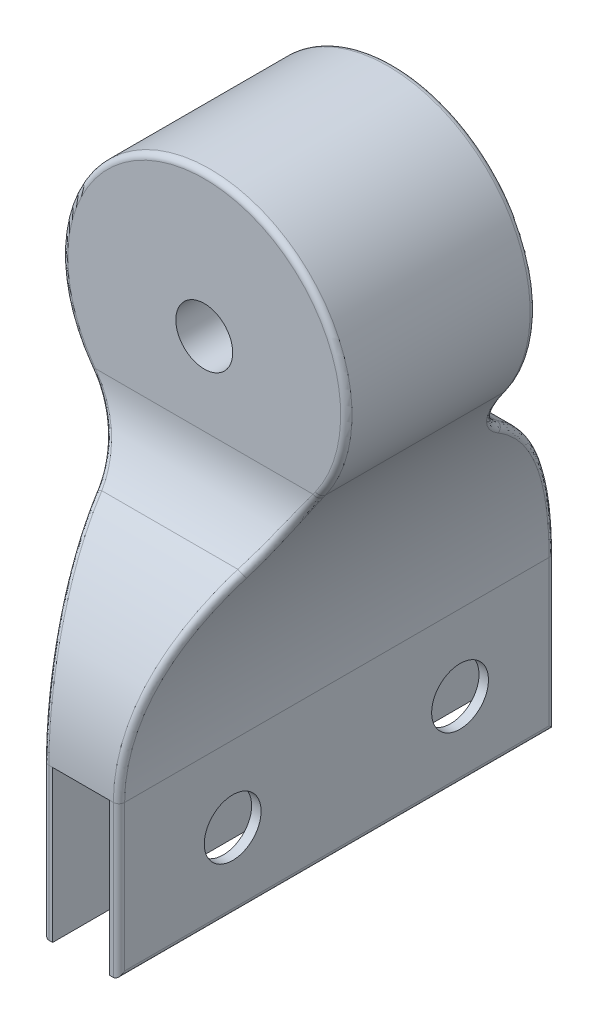
SolidWorks part; units mm, degrees
ref_plane "Front Plane" through (0, 0, 0) normal (0, 0, 1) x (1, 0, 0)
ref_plane "Top Plane" through (0, 0, 0) normal (0, 1, 0) x (1, 0, 0)
ref_plane "Right Plane" through (0, 0, 0) normal (1, 0, 0) x (0, 0, -1)
sketch "Sketch1" plane through (0, 0, 0) normal (0, 0, 1) x (1, 0, 0)
  line L9 (-2, -17.2071) -> (2, -17.2071)
  arc A1 (6.1096, -4.3501) -> (-6.1096, -4.3501) centre (0, 0) ccw
  arc A2 (-2, -17.2071) -> (-6.1096, -4.3501) centre (-24.1667, -17.2071) ccw
  arc A3 (2, -17.2071) -> (6.1096, -4.3501) centre (24.1667, -17.2071) cw
  dimension "D1" = 15
  dimension "D3" = 4
extrude "Boss-Extrude1" add sketch "Sketch1" along normal blind 23
sketch "Sketch2" plane through (0, 0, 0) normal (1, 0, 0) x (0, 0, -1)
  line L0 (-16.5, 7.5) -> (-6.5, 7.5)
  line L1 (0, 7.5) -> (-23, 7.5) construction
  line L2 (-6.5, 7.5) -> (-6.5, -4.3501)
  line L3 (-23, -4.3501) -> (0, -4.3501) construction
  line L5 (-16.5, -4.3501) -> (-16.5, 7.5)
  line L6 (0, -4.3501) -> (0, 7.5) construction
  line L8 (-23, -17.2071) -> (0, -17.2071) construction
  arc A0 (-18.318, -7.9462) -> (-4.682, -7.9462) centre (-11.5, -17.2071) ccw
  arc A2 (-18.318, -7.9462) -> (-16.5, -4.3501) centre (-20.9655, -4.3501) ccw
  arc A3 (-4.682, -7.9462) -> (-6.5, -4.3501) centre (-2.0345, -4.3501) cw
  dimension "D3" = 23
  dimension "D1" = 10
  dimension "D2" = 6.5
extrude "Cut-Extrude2" cut sketch "Sketch2" against normal blind 23 and the other way blind 23 flip side to cut
sketch "Sketch3" plane through (0, -17.2071, 0) normal (0, -1, 0) x (1, 0, 0)
  line L0 (-1.5, 23) -> (-1.5, 0)
  line L1 (-2, 23) -> (-1.5, 23)
  line L2 (-2, 23) -> (-2, 0)
  line L3 (-2, 0) -> (-1.5, 0)
  line L4 (2, 23) -> (2, 0)
  line L5 (1.5, 0) -> (1.5, 23)
  line L6 (1.5, 23) -> (2, 23)
  line L7 (1.5, 0) -> (2, 0)
  dimension "D1" = 0.5
  dimension "D2" = 0.5
extrude "Boss-Extrude4" add sketch "Sketch3" along normal blind 8
sketch "Sketch4" plane through (-2, 0, 0) normal (-1, 0, 0) x (0, 0, 1)
  line L0 (23, -25.2071) -> (0, -25.2071) construction
  line L2 (0, -25.2071) -> (0, -17.2071) construction
  circle A0 centre (17, -21.2071) radius 1.5
  circle A1 centre (5, -21.2071) radius 1.5
  dimension "D1" = 4
  dimension "D2" = 5
  dimension "D3" = 12
extrude "Cut-Extrude3" cut sketch "Sketch4" against normal blind 6
sketch "Sketch5" plane through (0, 0, 16.5) normal (0, 0, 1) x (1, 0, 0)
  circle A0 centre (0, 0) radius 1.5
extrude "Cut-Extrude4" cut sketch "Sketch5" against normal blind 16
fillet "Fillet5" radius 0.3 16 edges at (4.5542, -6.8769, 5.7163) (2.2849, -13.6643, 0.5593) (2.9549, -10.771, 21.0303) (4.9064, -6.2343, 16.917) (0, 7.5, 6.5) (0, 7.5, 16.5) (-2.9549, -10.771, 1.9697) (-4.9064, -6.2343, 6.083) (-4.5542, -6.8769, 17.2837) (-2.2849, -13.6643, 22.4407) (2, -21.2071, 0) (2, -25.2071, 11.5) (2, -21.2071, 23) (-2, -25.2071, 11.5) (-2, -21.2071, 23) (-2, -21.2071, 0)
